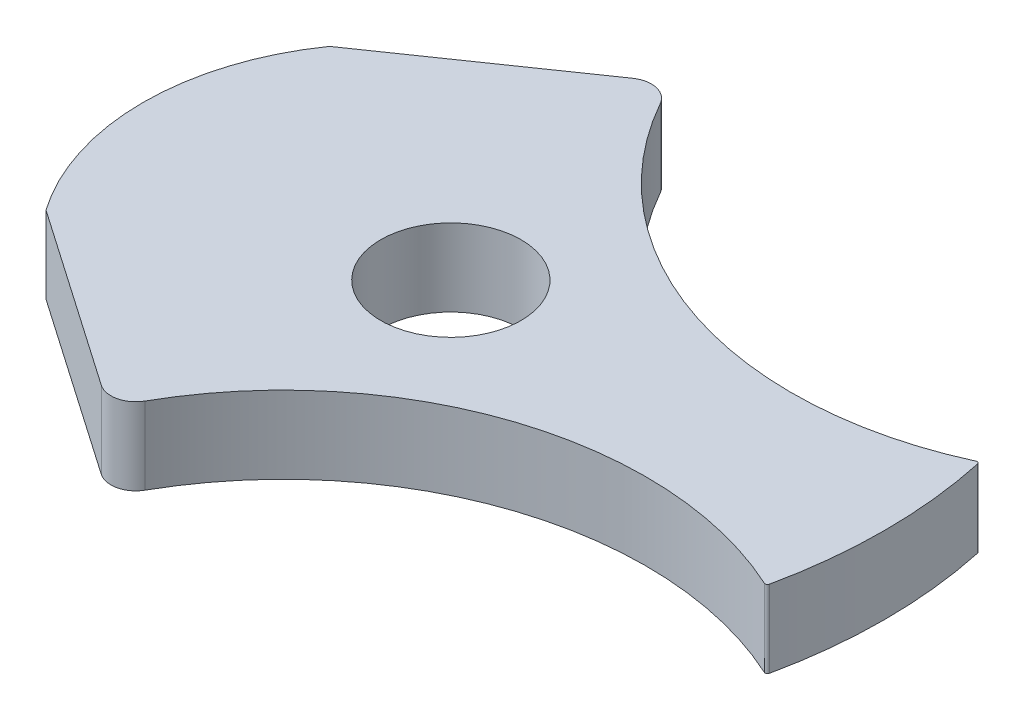
SolidWorks part; units mm, degrees
other "Markup1"
sketch "Sketch10" plane through (50.8, 12.7, 27.7659) normal (0.811, 0.2215, 0.5415) x (0.5842, -0.2583, -0.7694)
sketch "Sketch11" plane through (50.8, 12.7, 27.7659) normal (0.811, 0.2215, 0.5415) x (0.5842, -0.2583, -0.7694)
sketch "Sketch12" plane through (50.8, 7.9375, 27.7659) normal (0.811, 0.2215, 0.5415) x (0.5842, -0.2583, -0.7694)
material "AISI Type A2 Tool Steel"
ref_plane "Front Plane" through (0, 0, 0) normal (0, 0, 1) x (1, 0, 0)
ref_plane "Top Plane" through (0, 0, 0) normal (0, 1, 0) x (1, 0, 0)
ref_plane "Right Plane" through (0, 0, 0) normal (1, 0, 0) x (0, 0, -1)
other "Center of Mass"
sketch "Sketch1" plane through (0, 0, 0) normal (0, 1, 0) x (1, 0, 0)
  line L0 (0, 0) -> (-50000, 0) construction
  line L1 (-20.8065, 14.5688) -> (-20.8065, 0) construction
  line L2 (-20.8065, -14.5688) -> (-20.8065, 0) construction
  line L3 (49.5958, 10.9951) -> (49.5958, 0) construction
  line L4 (49.5958, -10.9951) -> (49.5958, 0) construction
  line L5 (0, 0) -> (0, 50000) construction
  line L6 (-20.8065, 14.5688) -> (0, 28.9594)
  line L7 (-20.8065, -14.5688) -> (0, -28.9594)
  line L8 (-20.8065, 14.5688) -> (0, 14.5688) construction
  line L9 (-20.8065, -14.5688) -> (0, -14.5688) construction
  arc A0 (-20.8065, 14.5688) -> (-20.8065, -14.5688) centre (0, 0) ccw
  arc A1 (49.5958, 10.9951) -> (49.5958, -10.9951) centre (0, 0) cw
  arc A2 (49.5958, 10.9951) -> (0, 28.9594) centre (33.7801, 44.7752) cw
  arc A3 (0, -28.9594) -> (49.5958, -10.9951) centre (33.7801, -44.7752) cw
  dimension "D1" = 25.4
  dimension "D2" = 25
  dimension "D4" = 70
  dimension "D3" = 50.8
  dimension "D6" = 37.2992
  dimension "D5" = 28.9594
extrude "Boss-Extrude1" add sketch "Sketch1" along normal blind 7.9375
sketch "Sketch3" plane through (0, 0, 0) normal (0, -1, 0) x (1, 0, 0)
  circle A0 centre (6.2319, 0) radius 7.2073
  dimension "D1" = 14.4145
fillet "Fillet3" radius 2.54 1 edges at (0, 3.9688, -28.9594)
fillet "Fillet4" radius 2.54 1 edges at (0, 3.9688, 28.9594)
extrude "Cut-Extrude2" cut sketch "Sketch3" against normal through all contours A0
sketch "Sketch7" plane through (0, 7.9375, 0) normal (0, 1, 0) x (1, 0, 0)
  line L0 (6.2319, 0) -> (50.8, 0) construction
  arc A0 (49.5958, -10.9951) -> (49.5958, 10.9951) centre (0, 0) ccw construction
sketch "Sketch9" plane through (0, 7.9375, 0) normal (0, 1, 0) x (1, 0, 0)
fillet "Fillet5" radius 0.254 2 edges at (49.5958, 3.9688, 10.9951) (49.5958, 3.9688, -10.9951)
